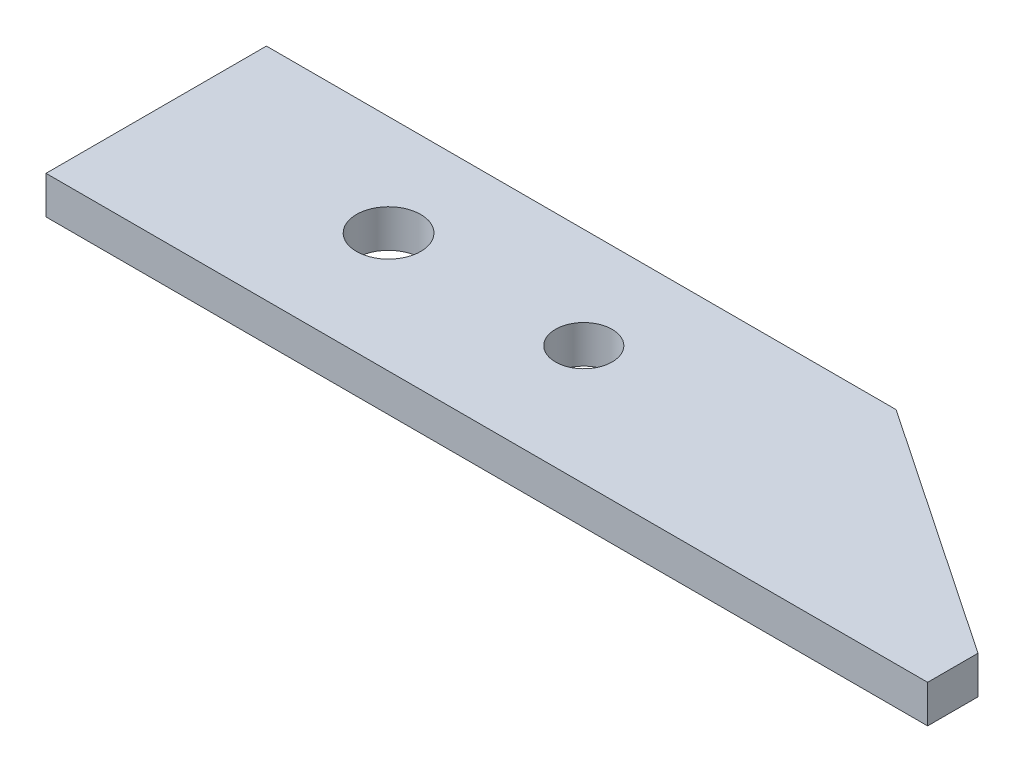
SolidWorks part; units mm, degrees
material "Maple"
ref_plane "Front Plane" through (0, 0, 0) normal (0, 0, 1) x (1, 0, 0)
ref_plane "Top Plane" through (0, 0, 0) normal (0, 1, 0) x (1, 0, 0)
ref_plane "Right Plane" through (0, 0, 0) normal (1, 0, 0) x (0, 0, -1)
sketch "Sketch1" plane through (0, 0, 0) normal (0, 1, 0) x (1, 0, 0)
  line L1 (0, 0) -> (140, 0)
  line L2 (0, 0) -> (0, 35)
  line L3 (0, 35) -> (140, 35)
  line L4 (140, 0) -> (140, 35)
  dimension "D1" = 35
extrude "Boss-Extrude1" add sketch "Sketch1" along normal blind 6
ref_plane "Plane1" through (0, 3, 0) normal (0, 1, 0) x (1, 0, 0)
sketch "Sketch2" plane through (0, 6, 0) normal (0, 1, 0) x (1, 0, 0)
  circle A0 centre (66.4, 19) radius 4.5
  circle A1 centre (35.4, 19) radius 5.1
  circle A2 centre (66.4, 19) radius 4 construction
  circle A3 centre (35.4, 19) radius 4 construction
  dimension "D1" = 9
  dimension "D2" = 10.2
extrude "Cut-Extrude1" cut sketch "Sketch2" against normal through all
sketch "Sketch3" plane through (0, 6, 0) normal (0, 1, 0) x (1, 0, 0)
  line L0 (140, 8) -> (100, 35)
  line L1 (140, 0) -> (140, 35) construction
  line L2 (140, 35) -> (0, 35) construction
  line L3 (100, 35) -> (140, 35)
  line L4 (140, 35) -> (140, 8)
  line L5 (0, 0) -> (140, 0) construction
  dimension "D1" = 8
  dimension "D2" = 40
extrude "Cut-Extrude2" cut sketch "Sketch3" against normal through all
